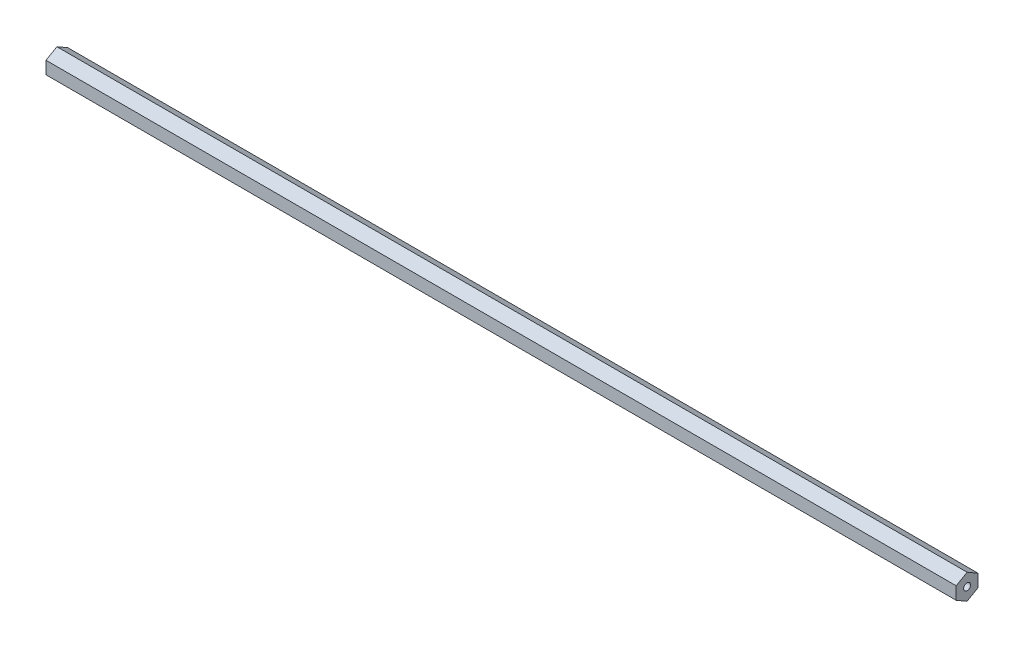
SolidWorks part; units mm, degrees
material "6061-T6 (SS)"
ref_plane "Front" through (0, 0, 0) normal (0, 0, 1) x (1, 0, 0)
ref_plane "Top" through (0, 0, 0) normal (0, 1, 0) x (1, 0, 0)
ref_plane "Right" through (0, 0, 0) normal (1, 0, 0) x (0, 0, -1)
ref_axis "Axis1" through (-80.9, 0, 0) along (1, 0, 0)
sketch "Sketch1" plane through (0, 0, 0) normal (1, 0, 0) x (0, 0, -1)
  line L1 (0, 7.3323) -> (-6.35, 3.6662)
  line L2 (-6.35, 3.6662) -> (-6.35, -3.6662)
  line L3 (-6.35, -3.6662) -> (0, -7.3323)
  line L4 (0, -7.3323) -> (6.35, -3.6662)
  line L5 (6.35, -3.6662) -> (6.35, 3.6662)
  line L6 (6.35, 3.6662) -> (0, 7.3323)
  circle A0 centre (0, 0) radius 6.35 construction
  dimension "D1" = 12.7
extrude "Boss-Extrude1" add sketch "Sketch1" along normal mid plane 530.225
hole_wizard "#10-32 Tapped Hole1" positions "Sketch2" profile "Sketch3" tap size "#10-32" standard "ANSI Inch"
sketch "Sketch2" plane through (265.1125, 0, 0) normal (1, 0, 0) x (0, 0, -1)
  point P0 (0, 0)
sketch "Sketch3" plane through (265.1125, 0, 0) normal (0, 1, 0) x (0, 0, -1)
  line L0 (0, 0) -> (0, 13.2529)
  line L1 (0, 13.2529) -> (2.0193, 12.0396)
  line L2 (2.0193, 12.0396) -> (2.0193, 0)
  line L5 (2.0193, 0) -> (0, 0)
  line L10 (0, 13.2529) -> (-2.0193, 12.0396) construction
  line L11 (0, -6.35) -> (0, 107.95) construction
  dimension "Tap Drill Dia." = 4.0386
  dimension "Tap Drill Depth" = 12.0396
  dimension "Drill Angle" = 118
cosmetic thread "Hole Thread1" parameters "D1"=9.652, "D2"=4.826
hole_wizard "#10-32 Tapped Hole2" positions "Sketch4" profile "Sketch5" tap size "#10-32" standard "ANSI Inch"
sketch "Sketch4" plane through (-265.1125, 0, 0) normal (-1, 0, 0) x (0, 0, 1)
  point P0 (0, 0)
sketch "Sketch5" plane through (-265.1125, 0, 0) normal (0, 1, 0) x (0, 0, 1)
  line L0 (0, 0) -> (0, 13.2529)
  line L1 (0, 13.2529) -> (2.0193, 12.0396)
  line L2 (2.0193, 12.0396) -> (2.0193, 0)
  line L5 (2.0193, 0) -> (0, 0)
  line L10 (0, 13.2529) -> (-2.0193, 12.0396) construction
  line L11 (0, -6.35) -> (0, 107.95) construction
  dimension "Tap Drill Dia." = 4.0386
  dimension "Tap Drill Depth" = 12.0396
  dimension "Drill Angle" = 118
cosmetic thread "Hole Thread2" parameters "D1"=9.652, "D2"=4.826
